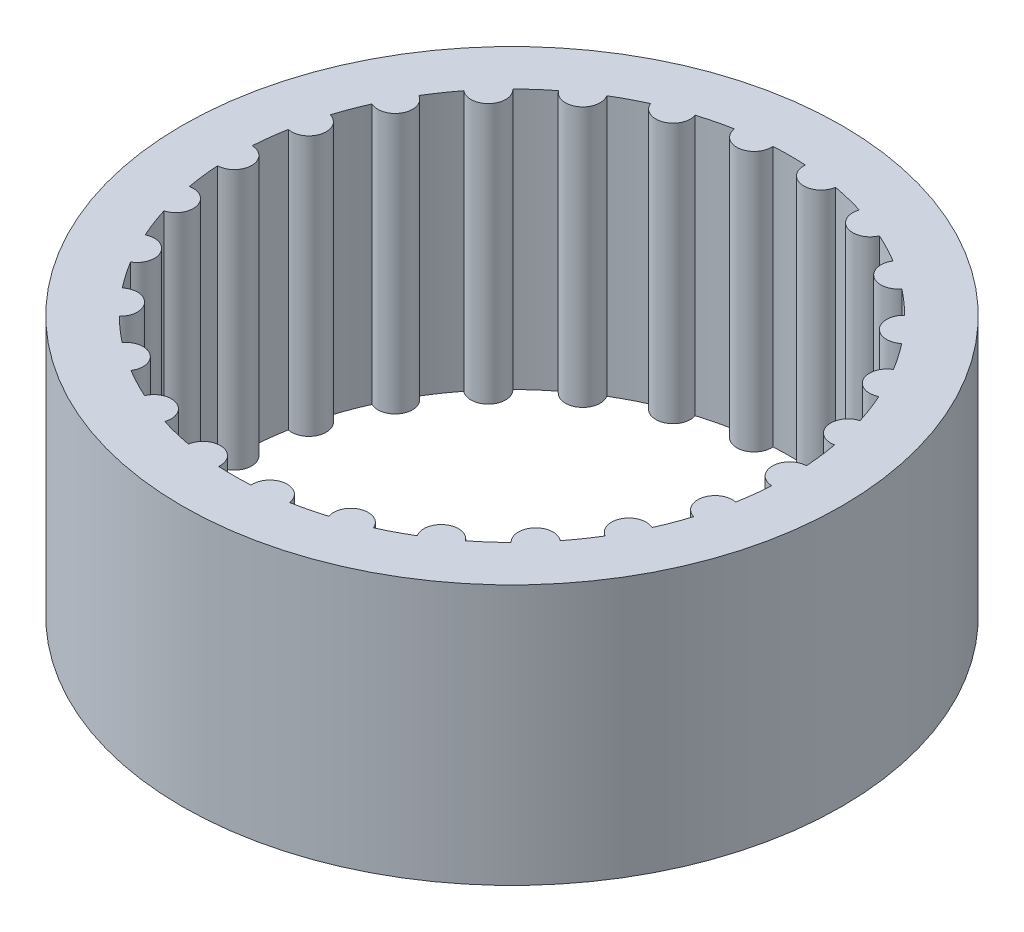
SolidWorks part; units mm, degrees
ref_plane "Front Plane" through (0, 0, 0) normal (0, 0, 1) x (1, 0, 0)
ref_plane "Top Plane" through (0, 0, 0) normal (0, 1, 0) x (1, 0, 0)
ref_plane "Right Plane" through (0, 0, 0) normal (1, 0, 0) x (0, 0, -1)
sketch "Sketch2" plane through (0, 0, 0) normal (0, 1, 0) x (1, 0, 0)
  line L0 (-15.4, 0) -> (14.4, 0) construction
  line L1 (0, 0) -> (0, -14.9128) construction
  line L2 (0, 0) -> (0, 14.9128) construction
  line L3 (-0.5, 0) -> (-0.5, -14.9128) construction
  line L4 (-0.5, 0) -> (-0.5, 14.9128) construction
  line L5 (14.4, 0) -> (15.5, 0) construction
  line L6 (0, 14.9128) -> (0, -14.9128) construction
  line L7 (5.9, 0) -> (9.1, 0) construction
  line L8 (5.9, 0) -> (7.5, 0)
  circle A0 centre (-0.5, 0) radius 16 construction
  circle A1 centre (15.5, 0) radius 1
  circle A2 centre (15.0351, -3.8291) radius 1
  circle A3 centre (13.6673, -7.4356) radius 1
  circle A4 centre (11.4762, -10.61) radius 1
  circle A5 centre (8.589, -13.1677) radius 1
  circle A6 centre (5.1737, -14.9603) radius 1
  circle A7 centre (1.4286, -15.8833) radius 1
  circle A8 centre (-2.4286, -15.8833) radius 1
  circle A9 centre (-6.1737, -14.9603) radius 1
  circle A10 centre (-9.589, -13.1677) radius 1
  circle A11 centre (-12.4762, -10.61) radius 1
  circle A12 centre (-14.6673, -7.4356) radius 1
  circle A13 centre (-16.0351, -3.8291) radius 1
  circle A14 centre (-16.5, 0) radius 1
  circle A15 centre (-16.0351, 3.8291) radius 1
  circle A16 centre (-14.6673, 7.4356) radius 1
  circle A17 centre (-12.4762, 10.61) radius 1
  circle A18 centre (-9.589, 13.1677) radius 1
  circle A19 centre (-6.1737, 14.9603) radius 1
  circle A20 centre (-2.4286, 15.8833) radius 1
  circle A21 centre (1.4286, 15.8833) radius 1
  circle A22 centre (5.1737, 14.9603) radius 1
  circle A23 centre (8.589, 13.1677) radius 1
  circle A24 centre (11.4762, 10.61) radius 1
  circle A25 centre (13.6673, 7.4356) radius 1
  circle A26 centre (15.0351, 3.8291) radius 1
  circle A27 centre (0, 0) radius 8
  circle A28 centre (8, 0) radius 2.1
  circle A29 centre (4, 6.9282) radius 2.1
  circle A30 centre (-4, 6.9282) radius 2.1
  circle A31 centre (-8, 0) radius 2.1
  circle A32 centre (-4, -6.9282) radius 2.1
  circle A33 centre (4, -6.9282) radius 2.1
  circle A34 centre (-1, 0) radius 8 construction
  circle A35 centre (3, -6.9282) radius 2.1
  circle A36 centre (-5, -6.9282) radius 2.1
  circle A37 centre (-9, 0) radius 2.1
  circle A38 centre (-5, 6.9282) radius 2.1
  circle A39 centre (3, 6.9282) radius 2.1
  circle A40 centre (7, 0) radius 2.1
  circle A41 centre (7.5, 0) radius 1.5
  circle A42 centre (3.5, -6.9282) radius 1.5
  circle A43 centre (-4.5, -6.9282) radius 1.5
  circle A44 centre (-8.5, 0) radius 1.5
  circle A45 centre (-4.5, 6.9282) radius 1.5
  circle A46 centre (3.5, 6.9282) radius 1.5
  spline S0 degree 4 poles (14.1521, 3.1658) (14.188, 3.1199) (14.2658, 3.0332) (14.3775, 2.9384) (14.515, 2.8555) (14.6203, 2.806) (14.6874, 2.778) (14.7412, 2.7556) (14.7939, 2.7309) (14.8442, 2.7016) (14.9616, 2.6171) (15.116, 2.4418) (15.2531, 2.163) (15.3044, 1.8261) (15.2781, 1.5454) (15.2134, 1.3341) (15.1457, 1.199) (15.0717, 1.0959) (14.999, 1.0246) (14.9346, 0.9749) (14.8529, 0.9144) (14.7598, 0.8351) (14.6613, 0.7318) (14.5658, 0.5985) (14.4899, 0.4547) (14.4445, 0.3242) (14.4198, 0.2202) (14.4058, 0.1237) (14.3997, 0.036) (14.399, -0.0233) (14.4055, -0.1232) (14.4175, -0.2057) (14.4353, -0.2848) (14.4589, -0.3638) (14.4955, -0.4601) (14.5538, -0.5777) (14.629, -0.6905) (14.7205, -0.7952) (14.8099, -0.8785) (14.886, -0.9397) (14.9653, -0.9969) (15.0394, -1.0608) (15.1018, -1.1365) (15.1543, -1.2193) (15.2086, -1.3292) (15.2563, -1.4688) (15.2881, -1.6381) (15.2945, -1.881) (15.2523, -2.1199) (15.1638, -2.3444) (15.0424, -2.5231) (14.9425, -2.6287) (14.8453, -2.7036) (14.7572, -2.7504) (14.6644, -2.7867) (14.5734, -2.827) (14.4636, -2.8857) (14.309, -2.9902) (14.1305, -3.1658) (13.9721, -3.435) (13.894, -3.7733) (13.9169, -4.0803) (13.9952, -4.3102) (14.0824, -4.4685) (14.1503, -4.5677) (14.21, -4.6429) (14.2706, -4.7176) (14.3202, -4.8002) (14.3654, -4.9109) (14.3993, -5.0496) (14.4169, -5.2624) (14.3843, -5.5009) (14.3041, -5.731) (14.178, -5.9418) (14.0479, -6.0957) (13.9108, -6.2086) (13.7771, -6.2844) (13.6546, -6.3259) (13.5506, -6.3413) (13.4467, -6.3556) (13.3441, -6.3782) (13.2186, -6.4164) (13.0491, -6.4902) (12.8504, -6.6239) (12.6494, -6.8484) (12.5061, -7.1523) (12.463, -7.451) (12.49, -7.6921) (12.5392, -7.8624) (12.5803, -7.968) (12.6183, -8.0504) (12.6544, -8.1336) (12.6783, -8.2214) (12.6929, -8.336) (12.6907, -8.4762) (12.6543, -8.6855) (12.5452, -8.9512) (12.3731, -9.1837) (12.1492, -9.3663) (11.9533, -9.4633) (11.8116, -9.5062) (11.6867, -9.5225) (11.5835, -9.517) (11.4812, -9.5034) (11.3782, -9.4969) (11.2749, -9.4982) (11.1721, -9.508) (11.0085, -9.5382) (10.791, -9.6158) (10.5438, -9.7787) (10.3474, -10.0243) (10.2402, -10.2686) (10.1943, -10.4842) (10.1853, -10.6384) (10.1931, -10.7705) (10.2091, -10.8795) (10.2256, -10.9662) (10.236, -11.0539) (10.2331, -11.1423) (10.2158, -11.2534) (10.1767, -11.3842) (10.0886, -11.5718) (9.9146, -11.8006) (9.6439, -12.0158) (9.3384, -12.1314) (9.0923, -12.1519) (8.9388, -12.1247) (8.8741, -12.1049) (8.8233, -12.0863) (8.76, -12.0622) (8.6577, -12.0268) (8.5127, -11.9913) (8.2954, -11.971) (8.0233, -12.0058) (7.7397, -12.12) (7.4775, -12.3303) (7.3093, -12.5758) (7.2277, -12.7964) (7.1948, -12.9647) (7.1831, -13.0729) (7.1774, -13.16) (7.1639, -13.2682) (7.1207, -13.3961) (7.0432, -13.5357) (6.8963, -13.7154) (6.6678, -13.8963) (6.3478, -14.0387) (6.02, -14.0727) (5.7619, -14.0269) (5.5985, -13.9438) (5.5126, -13.8801) (5.4018, -13.8057) (5.2599, -13.7303) (5.0524, -13.6565) (4.7738, -13.623) (4.4626, -13.6683) (4.1888, -13.7999) (3.9912, -13.9665) (3.8578, -14.1339) (3.7826, -14.2632) (3.7309, -14.3799) (3.6959, -14.48) (3.6689, -14.5606) (3.6251, -14.6573) (3.5494, -14.7647) (3.44, -14.8752) (3.2557, -15.006) (2.9928, -15.1201) (2.6515, -15.1757) (2.3406, -15.1291) (2.1258, -15.0338) (2.011, -14.9468) (1.9698, -14.909) (1.9317, -14.8681) (1.8954, -14.8255) (1.8499, -14.7726) (1.7735, -14.691) (1.6576, -14.5893) (1.4677, -14.4687) (1.2013, -14.3748) (0.8943, -14.3518) (0.5705, -14.4236) (0.3173, -14.5632) (0.1515, -14.7141) (0.0481, -14.8418) (-0.0114, -14.9289) (-0.057, -15.0001) (-0.1205, -15.0845) (-0.2167, -15.1711) (-0.3455, -15.2521) (-0.5484, -15.3356) (-0.8128, -15.3854) (-1.084, -15.3726) (-1.345, -15.2972) (-1.5435, -15.1922) (-1.6658, -15.0976) (-1.7547, -15.002) (-1.8112, -14.9128) (-1.8483, -14.8369) (-1.8948, -14.7422) (-1.9811, -14.5964) (-2.1305, -14.4153) (-2.3717, -14.2374) (-2.6941, -14.1243) (-3.0058, -14.1121) (-3.2798, -14.1742) (-3.4814, -14.2713) (-3.6077, -14.3581) (-3.6929, -14.4296) (-3.7443, -14.4763) (-3.7855, -14.5136) (-3.839, -14.5578) (-3.9718, -14.6426) (-4.2092, -14.7163) (-4.5379, -14.7232) (-4.871, -14.6233) (-5.1192, -14.4741) (-5.2872, -14.3161) (-5.3818, -14.1888) (-5.4416, -14.0686) (-5.4698, -13.9639) (-5.4862, -13.8788) (-5.5106, -13.7734) (-5.5628, -13.6112) (-5.6686, -13.4029) (-5.8615, -13.1808) (-6.1409, -13.0036) (-6.4324, -12.9205) (-6.707, -12.9139) (-6.9246, -12.958) (-7.0705, -13.0119) (-7.1719, -13.0612) (-7.2342, -13.0943) (-7.2842, -13.1203) (-7.3485, -13.1494) (-7.4504, -13.1813) (-7.5929, -13.1993) (-7.8225, -13.1875) (-8.1082, -13.1019) (-8.3607, -12.9481) (-8.5641, -12.7393) (-8.6869, -12.541) (-8.7459, -12.3913) (-8.7711, -12.2579) (-8.7697, -12.1482) (-8.7645, -12.0606) (-8.7633, -11.951) (-8.7731, -11.8212) (-8.8019, -11.6732) (-8.8729, -11.4717) (-9.0045, -11.25) (-9.2205, -11.0351) (-9.4997, -10.8905) (-9.7475, -10.8369) (-9.9383, -10.8322) (-10.0675, -10.8437) (-10.1698, -10.8609) (-10.2704, -10.8859) (-10.3717, -10.9089) (-10.4995, -10.9144) (-10.6499, -10.893) (-10.8644, -10.8236) (-11.1154, -10.6702) (-11.3185, -10.4608) (-11.4614, -10.2119) (-11.5248, -10.0134) (-11.5464, -9.8777) (-11.5487, -9.7646) (-11.5393, -9.6761) (-11.5169, -9.5902) (-11.4896, -9.5058) (-11.4606, -9.3988) (-11.4371, -9.2678) (-11.428, -9.1126) (-11.4489, -8.8917) (-11.5253, -8.6444) (-11.6806, -8.3917) (-11.9083, -8.1893) (-12.1461, -8.0664) (-12.3515, -8.0112) (-12.509, -7.9918) (-12.6408, -7.9895) (-12.7466, -7.9882) (-12.8744, -7.9638) (-13.0178, -7.9059) (-13.1692, -7.8114) (-13.319, -7.6747) (-13.472, -7.4805) (-13.5815, -7.2609) (-13.644, -7.0266) (-13.6529, -6.8129) (-13.6365, -6.6729) (-13.6064, -6.5605) (-13.5704, -6.4764) (-13.5232, -6.3982) (-13.4752, -6.3206) (-13.4215, -6.2199) (-13.3522, -6.0556) (-13.2972, -5.8178) (-13.3061, -5.5112) (-13.4183, -5.1858) (-13.5996, -4.9373) (-13.7884, -4.7826) (-13.9504, -4.6931) (-14.068, -4.6441) (-14.1647, -4.6121) (-14.2634, -4.587) (-14.3606, -4.5562) (-14.4721, -4.4972) (-14.5906, -4.4054) (-14.7415, -4.2409) (-14.8856, -3.984) (-14.9605, -3.7) (-14.9625, -3.4094) (-14.9171, -3.1994) (-14.8649, -3.0656) (-14.8048, -2.9613) (-14.7437, -2.886) (-14.6735, -2.8194) (-14.6048, -2.7515) (-14.5411, -2.6786) (-14.4829, -2.6013) (-14.3984, -2.4684) (-14.3099, -2.2678) (-14.2572, -1.9916) (-14.2948, -1.6527) (-14.4157, -1.3725) (-14.5648, -1.1806) (-14.7009, -1.0585) (-14.8015, -0.9857) (-14.886, -0.9336) (-14.9732, -0.8861) (-15.056, -0.8309) (-15.1453, -0.7457) (-15.2341, -0.6279) (-15.3021, -0.4979) (-15.3506, -0.3595) (-15.3784, -0.2422) (-15.3932, -0.1473) (-15.4005, -0.038) (-15.4007, 0.0312) (-15.3943, 0.133) (-15.3819, 0.2227) (-15.3632, 0.3082) (-15.3383, 0.3938) (-15.2991, 0.498) (-15.241, 0.614) (-15.1569, 0.7356) (-15.0521, 0.8388) (-14.947, 0.9) (-14.8417, 0.9596) (-14.7374, 1.0292) (-14.6222, 1.1253) (-14.4762, 1.2888) (-14.3483, 1.5104) (-14.2696, 1.788) (-14.2718, 2.0824) (-14.3338, 2.3297) (-14.4228, 2.5131) (-14.5089, 2.6398) (-14.5912, 2.7371) (-14.6628, 2.8095) (-14.7315, 2.8736) (-14.7874, 2.9388) (-14.8392, 3.0187) (-14.9, 3.1445) (-14.933, 3.2628) (-14.9484, 3.3663) (-14.9531, 3.4358) knots 0 0 0 0 0 0.003662 0.007324 0.009155 0.010071 0.010986 0.011902 0.012818 0.013733 0.014649 0.020984 0.02732 0.032959 0.035778 0.038598 0.041156 0.042436 0.043715 0.044995 0.046274 0.048833 0.051398 0.053964 0.05653 0.059096 0.059963 0.060831 0.062566 0.06386 0.065154 0.066448 0.067743 0.069037 0.070331 0.072919 0.075992 0.077529 0.079065 0.080602 0.082139 0.083675 0.085212 0.086754 0.088296 0.09138 0.094464 0.097548 0.103529 0.106519 0.10951 0.111075 0.112641 0.114207 0.115773 0.117339 0.118905 0.122036 0.127492 0.132948 0.138255 0.143562 0.146585 0.148096 0.149608 0.151119 0.15263 0.154142 0.155653 0.158618 0.161583 0.167513 0.170668 0.173824 0.176979 0.180135 0.181785 0.183435 0.185086 0.186736 0.188387 0.190037 0.193338 0.198334 0.203329 0.208757 0.214186 0.217039 0.218465 0.219892 0.221319 0.222745 0.224172 0.225598 0.228568 0.231538 0.237477 0.243509 0.246525 0.249541 0.251164 0.252787 0.25441 0.256033 0.257656 0.259279 0.260902 0.262525 0.268116 0.273708 0.279232 0.281995 0.284757 0.287531 0.288919 0.290306 0.291693 0.293081 0.294468 0.295855 0.298752 0.301648 0.307441 0.313806 0.320171 0.321875 0.322726 0.323578 0.32443 0.325282 0.326985 0.330392 0.333799 0.338942 0.344084 0.349371 0.354658 0.3574 0.358771 0.360142 0.361513 0.362884 0.365627 0.368572 0.371516 0.377406 0.383828 0.390249 0.39193 0.393611 0.395291 0.396972 0.400333 0.403695 0.409076 0.414457 0.419833 0.422521 0.425209 0.427878 0.429213 0.430548 0.431883 0.433218 0.435887 0.438758 0.441629 0.44737 0.453781 0.460191 0.46107 0.46195 0.462829 0.463708 0.464587 0.465466 0.467225 0.470742 0.474259 0.479542 0.484825 0.489836 0.494847 0.497504 0.498832 0.500161 0.501489 0.502818 0.505475 0.508247 0.51102 0.516564 0.52227 0.525123 0.527976 0.530631 0.531959 0.533286 0.534614 0.535941 0.538597 0.543936 0.549276 0.554531 0.559787 0.563284 0.566782 0.568531 0.569405 0.570279 0.571154 0.572028 0.573777 0.580153 0.586529 0.592383 0.595311 0.598238 0.600963 0.602326 0.603688 0.605051 0.606414 0.609139 0.614393 0.619646 0.62466 0.629675 0.633224 0.636772 0.638547 0.639434 0.640321 0.641208 0.642095 0.64387 0.647026 0.650182 0.656494 0.66242 0.665383 0.668345 0.671105 0.672484 0.673864 0.675243 0.676623 0.679382 0.682041 0.684701 0.690021 0.695473 0.700926 0.704188 0.705819 0.70745 0.709081 0.710712 0.712344 0.713975 0.717095 0.720216 0.726458 0.732287 0.735201 0.738116 0.739511 0.740907 0.742302 0.743698 0.745093 0.746488 0.749279 0.752059 0.754839 0.760398 0.765424 0.770449 0.773769 0.777088 0.778748 0.780408 0.782068 0.783727 0.786901 0.790075 0.793249 0.796422 0.802397 0.805385 0.808372 0.809808 0.811244 0.812679 0.814115 0.81555 0.816986 0.819857 0.825318 0.830779 0.83599 0.841201 0.844404 0.846006 0.847607 0.849209 0.850811 0.852412 0.854014 0.857107 0.8602 0.866387 0.872353 0.875336 0.878319 0.87984 0.881361 0.882882 0.884402 0.885923 0.887444 0.888965 0.890486 0.895823 0.90116 0.906397 0.911634 0.914757 0.916319 0.91788 0.919441 0.921003 0.922564 0.924126 0.927182 0.930238 0.931767 0.933295 0.934823 0.936351 0.937751 0.93915 0.940549 0.941949 0.943348 0.944747 0.947546 0.950087 0.952628 0.953898 0.955168 0.957709 0.960509 0.96331 0.96891 0.973663 0.978415 0.981621 0.984826 0.986428 0.988031 0.989634 0.991236 0.992332 0.993427 0.995618 1 1 1 1 1 construction
  spline S1 degree 4 poles (14.4, 0) (14.4, -0.018) (14.401, -0.0542) (14.4055, -0.1232) (14.4175, -0.2057) (14.4353, -0.2848) (14.4589, -0.3638) (14.4955, -0.4601) (14.5538, -0.5777) (14.629, -0.6905) (14.7205, -0.7952) (14.8099, -0.8785) (14.886, -0.9397) (14.9653, -0.9969) (15.0394, -1.0608) (15.1018, -1.1365) (15.1543, -1.2193) (15.2086, -1.3292) (15.2563, -1.4688) (15.2881, -1.6381) (15.2945, -1.881) (15.2523, -2.1199) (15.1638, -2.3444) (15.0424, -2.5231) (14.9425, -2.6287) (14.8453, -2.7036) (14.7572, -2.7504) (14.6644, -2.7867) (14.5734, -2.827) (14.4636, -2.8857) (14.309, -2.9902) (14.1305, -3.1658) (13.9721, -3.435) (13.894, -3.7733) (13.9169, -4.0803) (13.9952, -4.3102) (14.0824, -4.4685) (14.1503, -4.5677) (14.21, -4.6429) (14.2706, -4.7176) (14.3202, -4.8002) (14.3654, -4.9109) (14.3993, -5.0496) (14.4169, -5.2624) (14.3843, -5.5009) (14.3041, -5.731) (14.178, -5.9418) (14.0479, -6.0957) (13.9108, -6.2086) (13.7771, -6.2844) (13.6546, -6.3259) (13.5506, -6.3413) (13.4467, -6.3556) (13.3441, -6.3782) (13.2186, -6.4164) (13.0491, -6.4902) (12.8504, -6.6239) (12.6494, -6.8484) (12.5061, -7.1523) (12.463, -7.451) (12.49, -7.6921) (12.5392, -7.8624) (12.5803, -7.968) (12.6183, -8.0504) (12.6544, -8.1336) (12.6783, -8.2214) (12.6929, -8.336) (12.6907, -8.4762) (12.6543, -8.6855) (12.5452, -8.9512) (12.3731, -9.1837) (12.1492, -9.3663) (11.9533, -9.4633) (11.8116, -9.5062) (11.6867, -9.5225) (11.5835, -9.517) (11.4812, -9.5034) (11.3782, -9.4969) (11.2749, -9.4982) (11.1721, -9.508) (11.0085, -9.5382) (10.791, -9.6158) (10.5438, -9.7787) (10.3474, -10.0243) (10.2402, -10.2686) (10.1943, -10.4842) (10.1853, -10.6384) (10.1931, -10.7705) (10.2091, -10.8795) (10.2256, -10.9662) (10.236, -11.0539) (10.2331, -11.1423) (10.2158, -11.2534) (10.1767, -11.3842) (10.0886, -11.5718) (9.9146, -11.8006) (9.6439, -12.0158) (9.3384, -12.1314) (9.0923, -12.1519) (8.9388, -12.1247) (8.8741, -12.1049) (8.8233, -12.0863) (8.76, -12.0622) (8.6577, -12.0268) (8.5127, -11.9913) (8.2954, -11.971) (8.0233, -12.0058) (7.7397, -12.12) (7.4775, -12.3303) (7.3093, -12.5758) (7.2277, -12.7964) (7.1948, -12.9647) (7.1831, -13.0729) (7.1774, -13.16) (7.1639, -13.2682) (7.1207, -13.3961) (7.0432, -13.5357) (6.8963, -13.7154) (6.6678, -13.8963) (6.3478, -14.0387) (6.02, -14.0727) (5.7619, -14.0269) (5.5985, -13.9438) (5.5126, -13.8801) (5.4018, -13.8057) (5.2599, -13.7303) (5.0524, -13.6565) (4.7738, -13.623) (4.4626, -13.6683) (4.1888, -13.7999) (3.9912, -13.9665) (3.8578, -14.1339) (3.7826, -14.2632) (3.7309, -14.3799) (3.6959, -14.48) (3.6689, -14.5606) (3.6251, -14.6573) (3.5494, -14.7647) (3.44, -14.8752) (3.2557, -15.006) (2.9928, -15.1201) (2.6515, -15.1757) (2.3406, -15.1291) (2.1258, -15.0338) (2.011, -14.9468) (1.9698, -14.909) (1.9317, -14.8681) (1.8954, -14.8255) (1.8499, -14.7726) (1.7735, -14.691) (1.6576, -14.5893) (1.4677, -14.4687) (1.2013, -14.3748) (0.8943, -14.3518) (0.5705, -14.4236) (0.3173, -14.5632) (0.1515, -14.7141) (0.0481, -14.8418) (-0.0114, -14.9289) (-0.057, -15.0001) (-0.1205, -15.0845) (-0.2167, -15.1711) (-0.3455, -15.2521) (-0.5484, -15.3356) (-0.8128, -15.3854) (-1.084, -15.3726) (-1.345, -15.2972) (-1.5435, -15.1922) (-1.6658, -15.0976) (-1.7547, -15.002) (-1.8112, -14.9128) (-1.8483, -14.8369) (-1.8948, -14.7422) (-1.9811, -14.5964) (-2.1305, -14.4153) (-2.3717, -14.2374) (-2.6941, -14.1243) (-3.0058, -14.1121) (-3.2798, -14.1742) (-3.4814, -14.2713) (-3.6077, -14.3581) (-3.6929, -14.4296) (-3.7443, -14.4763) (-3.7855, -14.5136) (-3.839, -14.5578) (-3.9718, -14.6426) (-4.2092, -14.7163) (-4.5379, -14.7232) (-4.871, -14.6233) (-5.1192, -14.4741) (-5.2872, -14.3161) (-5.3818, -14.1888) (-5.4416, -14.0686) (-5.4698, -13.9639) (-5.4862, -13.8788) (-5.5106, -13.7734) (-5.5628, -13.6112) (-5.6686, -13.4029) (-5.8615, -13.1808) (-6.1409, -13.0036) (-6.4324, -12.9205) (-6.707, -12.9139) (-6.9246, -12.958) (-7.0705, -13.0119) (-7.1719, -13.0612) (-7.2342, -13.0943) (-7.2842, -13.1203) (-7.3485, -13.1494) (-7.4504, -13.1813) (-7.5929, -13.1993) (-7.8225, -13.1875) (-8.1082, -13.1019) (-8.3607, -12.9481) (-8.5641, -12.7393) (-8.6869, -12.541) (-8.7459, -12.3913) (-8.7711, -12.2579) (-8.7697, -12.1482) (-8.7645, -12.0606) (-8.7633, -11.951) (-8.7731, -11.8212) (-8.8019, -11.6732) (-8.8729, -11.4717) (-9.0045, -11.25) (-9.2205, -11.0351) (-9.4997, -10.8905) (-9.7475, -10.8369) (-9.9383, -10.8322) (-10.0675, -10.8437) (-10.1698, -10.8609) (-10.2704, -10.8859) (-10.3717, -10.9089) (-10.4995, -10.9144) (-10.6499, -10.893) (-10.8644, -10.8236) (-11.1154, -10.6702) (-11.3185, -10.4608) (-11.4614, -10.2119) (-11.5248, -10.0134) (-11.5464, -9.8777) (-11.5487, -9.7646) (-11.5393, -9.6761) (-11.5169, -9.5902) (-11.4896, -9.5058) (-11.4606, -9.3988) (-11.4371, -9.2678) (-11.428, -9.1126) (-11.4489, -8.8917) (-11.5253, -8.6444) (-11.6806, -8.3917) (-11.9083, -8.1893) (-12.1461, -8.0664) (-12.3515, -8.0112) (-12.509, -7.9918) (-12.6408, -7.9895) (-12.7466, -7.9882) (-12.8744, -7.9638) (-13.0178, -7.9059) (-13.1692, -7.8114) (-13.319, -7.6747) (-13.472, -7.4805) (-13.5815, -7.2609) (-13.644, -7.0266) (-13.6529, -6.8129) (-13.6365, -6.6729) (-13.6064, -6.5605) (-13.5704, -6.4764) (-13.5232, -6.3982) (-13.4752, -6.3206) (-13.4215, -6.2199) (-13.3522, -6.0556) (-13.2972, -5.8178) (-13.3061, -5.5112) (-13.4183, -5.1858) (-13.5996, -4.9373) (-13.7884, -4.7826) (-13.9504, -4.6931) (-14.068, -4.6441) (-14.1647, -4.6121) (-14.2634, -4.587) (-14.3606, -4.5562) (-14.4721, -4.4972) (-14.5906, -4.4054) (-14.7415, -4.2409) (-14.8856, -3.984) (-14.9605, -3.7) (-14.9625, -3.4094) (-14.9171, -3.1994) (-14.8649, -3.0656) (-14.8048, -2.9613) (-14.7437, -2.886) (-14.6735, -2.8194) (-14.6048, -2.7515) (-14.5411, -2.6786) (-14.4829, -2.6013) (-14.3984, -2.4684) (-14.3099, -2.2678) (-14.2572, -1.9916) (-14.2948, -1.6527) (-14.4157, -1.3725) (-14.5648, -1.1806) (-14.7009, -1.0585) (-14.8015, -0.9857) (-14.886, -0.9336) (-14.9732, -0.8861) (-15.056, -0.8309) (-15.1453, -0.7457) (-15.2341, -0.6279) (-15.3021, -0.4979) (-15.3506, -0.3595) (-15.3784, -0.2422) (-15.3932, -0.1473) (-15.3988, -0.0635) (-15.4, -0.0212) (-15.4, 0) knots 0.062566 0.062566 0.062566 0.062566 0.062566 0.06386 0.065154 0.066448 0.067743 0.069037 0.070331 0.072919 0.075992 0.077529 0.079065 0.080602 0.082139 0.083675 0.085212 0.086754 0.088296 0.09138 0.094464 0.097548 0.103529 0.106519 0.10951 0.111075 0.112641 0.114207 0.115773 0.117339 0.118905 0.122036 0.127492 0.132948 0.138255 0.143562 0.146585 0.148096 0.149608 0.151119 0.15263 0.154142 0.155653 0.158618 0.161583 0.167513 0.170668 0.173824 0.176979 0.180135 0.181785 0.183435 0.185086 0.186736 0.188387 0.190037 0.193338 0.198334 0.203329 0.208757 0.214186 0.217039 0.218465 0.219892 0.221319 0.222745 0.224172 0.225598 0.228568 0.231538 0.237477 0.243509 0.246525 0.249541 0.251164 0.252787 0.25441 0.256033 0.257656 0.259279 0.260902 0.262525 0.268116 0.273708 0.279232 0.281995 0.284757 0.287531 0.288919 0.290306 0.291693 0.293081 0.294468 0.295855 0.298752 0.301648 0.307441 0.313806 0.320171 0.321875 0.322726 0.323578 0.32443 0.325282 0.326985 0.330392 0.333799 0.338942 0.344084 0.349371 0.354658 0.3574 0.358771 0.360142 0.361513 0.362884 0.365627 0.368572 0.371516 0.377406 0.383828 0.390249 0.39193 0.393611 0.395291 0.396972 0.400333 0.403695 0.409076 0.414457 0.419833 0.422521 0.425209 0.427878 0.429213 0.430548 0.431883 0.433218 0.435887 0.438758 0.441629 0.44737 0.453781 0.460191 0.46107 0.46195 0.462829 0.463708 0.464587 0.465466 0.467225 0.470742 0.474259 0.479542 0.484825 0.489836 0.494847 0.497504 0.498832 0.500161 0.501489 0.502818 0.505475 0.508247 0.51102 0.516564 0.52227 0.525123 0.527976 0.530631 0.531959 0.533286 0.534614 0.535941 0.538597 0.543936 0.549276 0.554531 0.559787 0.563284 0.566782 0.568531 0.569405 0.570279 0.571154 0.572028 0.573777 0.580153 0.586529 0.592383 0.595311 0.598238 0.600963 0.602326 0.603688 0.605051 0.606414 0.609139 0.614393 0.619646 0.62466 0.629675 0.633224 0.636772 0.638547 0.639434 0.640321 0.641208 0.642095 0.64387 0.647026 0.650182 0.656494 0.66242 0.665383 0.668345 0.671105 0.672484 0.673864 0.675243 0.676623 0.679382 0.682041 0.684701 0.690021 0.695473 0.700926 0.704188 0.705819 0.70745 0.709081 0.710712 0.712344 0.713975 0.717095 0.720216 0.726458 0.732287 0.735201 0.738116 0.739511 0.740907 0.742302 0.743698 0.745093 0.746488 0.749279 0.752059 0.754839 0.760398 0.765424 0.770449 0.773769 0.777088 0.778748 0.780408 0.782068 0.783727 0.786901 0.790075 0.793249 0.796422 0.802397 0.805385 0.808372 0.809808 0.811244 0.812679 0.814115 0.81555 0.816986 0.819857 0.825318 0.830779 0.83599 0.841201 0.844404 0.846006 0.847607 0.849209 0.850811 0.852412 0.854014 0.857107 0.8602 0.866387 0.872353 0.875336 0.878319 0.87984 0.881361 0.882882 0.884402 0.885923 0.887444 0.888965 0.890486 0.895823 0.90116 0.906397 0.911634 0.914757 0.916319 0.91788 0.919441 0.921003 0.922564 0.924126 0.927182 0.930238 0.931767 0.933295 0.934823 0.936351 0.936351 0.936351 0.936351 0.936351
  spline S2 degree 4 poles (14.4, 0) (14.4, 0.018) (14.401, 0.0542) (14.4055, 0.1232) (14.4175, 0.2057) (14.4353, 0.2848) (14.4589, 0.3638) (14.4955, 0.4601) (14.5538, 0.5777) (14.629, 0.6905) (14.7205, 0.7952) (14.8099, 0.8785) (14.886, 0.9397) (14.9653, 0.9969) (15.0394, 1.0608) (15.1018, 1.1365) (15.1543, 1.2193) (15.2086, 1.3292) (15.2563, 1.4688) (15.2881, 1.6381) (15.2945, 1.881) (15.2523, 2.1199) (15.1638, 2.3444) (15.0424, 2.5231) (14.9425, 2.6287) (14.8453, 2.7036) (14.7572, 2.7504) (14.6644, 2.7867) (14.5734, 2.827) (14.4636, 2.8857) (14.309, 2.9902) (14.1305, 3.1658) (13.9721, 3.435) (13.894, 3.7733) (13.9169, 4.0803) (13.9952, 4.3102) (14.0824, 4.4685) (14.1503, 4.5677) (14.21, 4.6429) (14.2706, 4.7176) (14.3202, 4.8002) (14.3654, 4.9109) (14.3993, 5.0496) (14.4169, 5.2624) (14.3843, 5.5009) (14.3041, 5.731) (14.178, 5.9418) (14.0479, 6.0957) (13.9108, 6.2086) (13.7771, 6.2844) (13.6546, 6.3259) (13.5506, 6.3413) (13.4467, 6.3556) (13.3441, 6.3782) (13.2186, 6.4164) (13.0491, 6.4902) (12.8504, 6.6239) (12.6494, 6.8484) (12.5061, 7.1523) (12.463, 7.451) (12.49, 7.6921) (12.5392, 7.8624) (12.5803, 7.968) (12.6183, 8.0504) (12.6544, 8.1336) (12.6783, 8.2214) (12.6929, 8.336) (12.6907, 8.4762) (12.6543, 8.6855) (12.5452, 8.9512) (12.3731, 9.1837) (12.1492, 9.3663) (11.9533, 9.4633) (11.8116, 9.5062) (11.6867, 9.5225) (11.5835, 9.517) (11.4812, 9.5034) (11.3782, 9.4969) (11.2749, 9.4982) (11.1721, 9.508) (11.0085, 9.5382) (10.791, 9.6158) (10.5438, 9.7787) (10.3474, 10.0243) (10.2402, 10.2686) (10.1943, 10.4842) (10.1853, 10.6384) (10.1931, 10.7705) (10.2091, 10.8795) (10.2256, 10.9662) (10.236, 11.0539) (10.2331, 11.1423) (10.2158, 11.2534) (10.1767, 11.3842) (10.0886, 11.5718) (9.9146, 11.8006) (9.6439, 12.0158) (9.3384, 12.1314) (9.0923, 12.1519) (8.9388, 12.1247) (8.8741, 12.1049) (8.8233, 12.0863) (8.76, 12.0622) (8.6577, 12.0268) (8.5127, 11.9913) (8.2954, 11.971) (8.0233, 12.0058) (7.7397, 12.12) (7.4775, 12.3303) (7.3093, 12.5758) (7.2277, 12.7964) (7.1948, 12.9647) (7.1831, 13.0729) (7.1774, 13.16) (7.1639, 13.2682) (7.1207, 13.3961) (7.0432, 13.5357) (6.8963, 13.7154) (6.6678, 13.8963) (6.3478, 14.0387) (6.02, 14.0727) (5.7619, 14.0269) (5.5985, 13.9438) (5.5126, 13.8801) (5.4018, 13.8057) (5.2599, 13.7303) (5.0524, 13.6565) (4.7738, 13.623) (4.4626, 13.6683) (4.1888, 13.7999) (3.9912, 13.9665) (3.8578, 14.1339) (3.7826, 14.2632) (3.7309, 14.3799) (3.6959, 14.48) (3.6689, 14.5606) (3.6251, 14.6573) (3.5494, 14.7647) (3.44, 14.8752) (3.2557, 15.006) (2.9928, 15.1201) (2.6515, 15.1757) (2.3406, 15.1291) (2.1258, 15.0338) (2.011, 14.9468) (1.9698, 14.909) (1.9317, 14.8681) (1.8954, 14.8255) (1.8499, 14.7726) (1.7735, 14.691) (1.6576, 14.5893) (1.4677, 14.4687) (1.2013, 14.3748) (0.8943, 14.3518) (0.5705, 14.4236) (0.3173, 14.5632) (0.1515, 14.7141) (0.0481, 14.8418) (-0.0114, 14.9289) (-0.057, 15) (-0.1205, 15.0845) (-0.2167, 15.1711) (-0.3455, 15.2521) (-0.5484, 15.3356) (-0.8128, 15.3854) (-1.084, 15.3726) (-1.345, 15.2972) (-1.5435, 15.1922) (-1.6658, 15.0976) (-1.7547, 15.002) (-1.8112, 14.9128) (-1.8483, 14.8369) (-1.8948, 14.7422) (-1.9811, 14.5964) (-2.1305, 14.4153) (-2.3717, 14.2374) (-2.6941, 14.1243) (-3.0058, 14.1121) (-3.2798, 14.1742) (-3.4814, 14.2713) (-3.6077, 14.3581) (-3.6929, 14.4296) (-3.7443, 14.4763) (-3.7855, 14.5136) (-3.839, 14.5578) (-3.9718, 14.6426) (-4.2092, 14.7163) (-4.5379, 14.7232) (-4.871, 14.6233) (-5.1192, 14.4741) (-5.2872, 14.3161) (-5.3818, 14.1887) (-5.4416, 14.0686) (-5.4698, 13.9639) (-5.4862, 13.8788) (-5.5106, 13.7734) (-5.5628, 13.6112) (-5.6686, 13.4029) (-5.8615, 13.1808) (-6.1409, 13.0036) (-6.4324, 12.9205) (-6.707, 12.9139) (-6.9246, 12.958) (-7.0705, 13.0119) (-7.1719, 13.0612) (-7.2342, 13.0943) (-7.2842, 13.1203) (-7.3485, 13.1494) (-7.4504, 13.1813) (-7.5929, 13.1993) (-7.8225, 13.1875) (-8.1082, 13.1019) (-8.3607, 12.9481) (-8.5641, 12.7393) (-8.6869, 12.541) (-8.7459, 12.3913) (-8.7711, 12.2579) (-8.7697, 12.1482) (-8.7645, 12.0606) (-8.7633, 11.951) (-8.7731, 11.8212) (-8.8019, 11.6732) (-8.8729, 11.4717) (-9.0045, 11.25) (-9.2205, 11.0351) (-9.4997, 10.8905) (-9.7475, 10.8369) (-9.9383, 10.8322) (-10.0675, 10.8437) (-10.1698, 10.8609) (-10.2704, 10.8859) (-10.3717, 10.9089) (-10.4995, 10.9144) (-10.6499, 10.893) (-10.8644, 10.8236) (-11.1154, 10.6702) (-11.3185, 10.4608) (-11.4614, 10.2119) (-11.5248, 10.0134) (-11.5464, 9.8777) (-11.5487, 9.7646) (-11.5393, 9.6761) (-11.5169, 9.5902) (-11.4896, 9.5058) (-11.4606, 9.3988) (-11.4371, 9.2678) (-11.428, 9.1126) (-11.4489, 8.8917) (-11.5253, 8.6444) (-11.6806, 8.3917) (-11.9083, 8.1893) (-12.1461, 8.0664) (-12.3515, 8.0112) (-12.509, 7.9918) (-12.6408, 7.9895) (-12.7466, 7.9882) (-12.8744, 7.9638) (-13.0178, 7.9059) (-13.1692, 7.8114) (-13.319, 7.6747) (-13.472, 7.4805) (-13.5815, 7.2609) (-13.644, 7.0266) (-13.6529, 6.8129) (-13.6365, 6.6728) (-13.6064, 6.5605) (-13.5704, 6.4764) (-13.5232, 6.3982) (-13.4752, 6.3206) (-13.4215, 6.2199) (-13.3522, 6.0556) (-13.2972, 5.8178) (-13.3061, 5.5112) (-13.4183, 5.1858) (-13.5996, 4.9373) (-13.7884, 4.7826) (-13.9504, 4.6931) (-14.068, 4.6441) (-14.1647, 4.6121) (-14.2634, 4.587) (-14.3606, 4.5562) (-14.4721, 4.4972) (-14.5906, 4.4054) (-14.7415, 4.2409) (-14.8856, 3.984) (-14.9605, 3.7) (-14.9625, 3.4094) (-14.9171, 3.1994) (-14.8649, 3.0655) (-14.8048, 2.9613) (-14.7437, 2.886) (-14.6735, 2.8194) (-14.6048, 2.7515) (-14.5411, 2.6786) (-14.4829, 2.6013) (-14.3984, 2.4684) (-14.3099, 2.2678) (-14.2572, 1.9916) (-14.2948, 1.6527) (-14.4157, 1.3725) (-14.5648, 1.1806) (-14.7009, 1.0585) (-14.8015, 0.9857) (-14.886, 0.9336) (-14.9732, 0.8861) (-15.056, 0.8309) (-15.1453, 0.7457) (-15.2341, 0.6279) (-15.3021, 0.4979) (-15.3506, 0.3595) (-15.3784, 0.2422) (-15.3932, 0.1473) (-15.3988, 0.0635) (-15.4, 0.0212) (-15.4, 0) knots 0.062566 0.062566 0.062566 0.062566 0.062566 0.06386 0.065154 0.066448 0.067743 0.069037 0.070331 0.072919 0.075992 0.077529 0.079065 0.080602 0.082139 0.083675 0.085212 0.086754 0.088296 0.09138 0.094464 0.097548 0.103529 0.106519 0.10951 0.111075 0.112641 0.114207 0.115773 0.117339 0.118905 0.122036 0.127492 0.132948 0.138255 0.143562 0.146585 0.148096 0.149608 0.151119 0.15263 0.154142 0.155653 0.158618 0.161583 0.167513 0.170668 0.173824 0.176979 0.180135 0.181785 0.183435 0.185086 0.186736 0.188387 0.190037 0.193338 0.198334 0.203329 0.208757 0.214186 0.217039 0.218465 0.219892 0.221319 0.222745 0.224172 0.225598 0.228568 0.231538 0.237477 0.243509 0.246525 0.249541 0.251164 0.252787 0.25441 0.256033 0.257656 0.259279 0.260902 0.262525 0.268116 0.273708 0.279232 0.281995 0.284757 0.287531 0.288919 0.290306 0.291693 0.293081 0.294468 0.295855 0.298752 0.301648 0.307441 0.313806 0.320171 0.321875 0.322726 0.323578 0.32443 0.325282 0.326985 0.330392 0.333799 0.338942 0.344084 0.349371 0.354658 0.3574 0.358771 0.360142 0.361513 0.362884 0.365627 0.368572 0.371516 0.377406 0.383828 0.390249 0.39193 0.393611 0.395291 0.396972 0.400333 0.403695 0.409076 0.414457 0.419833 0.422521 0.425209 0.427878 0.429213 0.430548 0.431883 0.433218 0.435887 0.438758 0.441629 0.44737 0.453781 0.460191 0.46107 0.46195 0.462829 0.463708 0.464587 0.465466 0.467225 0.470742 0.474259 0.479542 0.484825 0.489836 0.494847 0.497504 0.498832 0.500161 0.501489 0.502818 0.505475 0.508247 0.51102 0.516564 0.52227 0.525123 0.527976 0.530631 0.531959 0.533286 0.534614 0.535941 0.538597 0.543936 0.549276 0.554531 0.559787 0.563284 0.566782 0.568531 0.569405 0.570279 0.571154 0.572028 0.573777 0.580153 0.586529 0.592383 0.595311 0.598238 0.600963 0.602326 0.603688 0.605051 0.606414 0.609139 0.614393 0.619646 0.62466 0.629675 0.633224 0.636772 0.638547 0.639434 0.640321 0.641208 0.642095 0.64387 0.647026 0.650182 0.656494 0.66242 0.665383 0.668345 0.671105 0.672484 0.673864 0.675243 0.676623 0.679382 0.682041 0.684701 0.690021 0.695473 0.700926 0.704188 0.705819 0.70745 0.709081 0.710712 0.712344 0.713975 0.717095 0.720216 0.726458 0.732287 0.735201 0.738116 0.739511 0.740907 0.742302 0.743698 0.745093 0.746488 0.749279 0.752059 0.754839 0.760398 0.765424 0.770449 0.773769 0.777088 0.778748 0.780408 0.782068 0.783727 0.786901 0.790075 0.793249 0.796422 0.802397 0.805385 0.808372 0.809808 0.811244 0.812679 0.814115 0.81555 0.816986 0.819857 0.825318 0.830779 0.83599 0.841201 0.844404 0.846006 0.847607 0.849209 0.850811 0.852412 0.854014 0.857107 0.8602 0.866387 0.872353 0.875336 0.878319 0.87984 0.881361 0.882882 0.884402 0.885923 0.887444 0.888965 0.890486 0.895823 0.90116 0.906397 0.911634 0.914757 0.916319 0.91788 0.919441 0.921003 0.922564 0.924126 0.927182 0.930238 0.931767 0.933295 0.934823 0.936351 0.936351 0.936351 0.936351 0.936351
  spline S3 degree 4 poles (-15.4, 0) (-15.4, -0.018) (-15.401, -0.0542) (-15.4055, -0.1232) (-15.4175, -0.2057) (-15.4353, -0.2848) (-15.4589, -0.3638) (-15.4955, -0.4601) (-15.5538, -0.5777) (-15.629, -0.6905) (-15.7205, -0.7952) (-15.8099, -0.8785) (-15.886, -0.9397) (-15.9653, -0.9969) (-16.0394, -1.0608) (-16.1018, -1.1365) (-16.1543, -1.2193) (-16.2086, -1.3292) (-16.2563, -1.4688) (-16.2881, -1.6381) (-16.2945, -1.881) (-16.2523, -2.1199) (-16.1638, -2.3444) (-16.0424, -2.5231) (-15.9425, -2.6287) (-15.8453, -2.7036) (-15.7572, -2.7504) (-15.6644, -2.7867) (-15.5734, -2.827) (-15.4636, -2.8857) (-15.309, -2.9902) (-15.1305, -3.1658) (-14.9721, -3.435) (-14.894, -3.7733) (-14.9169, -4.0803) (-14.9952, -4.3102) (-15.0824, -4.4685) (-15.1503, -4.5677) (-15.21, -4.6429) (-15.2706, -4.7176) (-15.3202, -4.8002) (-15.3654, -4.9109) (-15.3993, -5.0496) (-15.4169, -5.2624) (-15.3843, -5.5009) (-15.3041, -5.731) (-15.178, -5.9418) (-15.0479, -6.0957) (-14.9108, -6.2086) (-14.7771, -6.2844) (-14.6546, -6.3259) (-14.5506, -6.3413) (-14.4467, -6.3556) (-14.3441, -6.3782) (-14.2186, -6.4164) (-14.0491, -6.4902) (-13.8504, -6.6239) (-13.6494, -6.8484) (-13.5061, -7.1523) (-13.463, -7.451) (-13.49, -7.6921) (-13.5392, -7.8624) (-13.5803, -7.968) (-13.6183, -8.0504) (-13.6544, -8.1336) (-13.6783, -8.2214) (-13.6929, -8.336) (-13.6907, -8.4762) (-13.6543, -8.6855) (-13.5452, -8.9512) (-13.3731, -9.1837) (-13.1492, -9.3663) (-12.9533, -9.4633) (-12.8116, -9.5062) (-12.6867, -9.5225) (-12.5835, -9.517) (-12.4812, -9.5034) (-12.3782, -9.4969) (-12.2749, -9.4982) (-12.1721, -9.508) (-12.0085, -9.5382) (-11.791, -9.6158) (-11.5438, -9.7787) (-11.3474, -10.0243) (-11.2402, -10.2686) (-11.1943, -10.4842) (-11.1853, -10.6384) (-11.1931, -10.7705) (-11.2091, -10.8795) (-11.2256, -10.9662) (-11.236, -11.0539) (-11.2331, -11.1423) (-11.2158, -11.2534) (-11.1767, -11.3842) (-11.0886, -11.5718) (-10.9146, -11.8006) (-10.6439, -12.0158) (-10.3384, -12.1314) (-10.0923, -12.1519) (-9.9388, -12.1247) (-9.8741, -12.1049) (-9.8233, -12.0863) (-9.76, -12.0622) (-9.6577, -12.0268) (-9.5127, -11.9913) (-9.2954, -11.971) (-9.0233, -12.0058) (-8.7397, -12.12) (-8.4775, -12.3303) (-8.3093, -12.5758) (-8.2277, -12.7964) (-8.1948, -12.9647) (-8.1831, -13.0729) (-8.1774, -13.16) (-8.1639, -13.2682) (-8.1207, -13.3961) (-8.0432, -13.5357) (-7.8963, -13.7154) (-7.6678, -13.8963) (-7.3478, -14.0387) (-7.02, -14.0727) (-6.7619, -14.0269) (-6.5985, -13.9438) (-6.5126, -13.8801) (-6.4018, -13.8057) (-6.2599, -13.7303) (-6.0524, -13.6565) (-5.7738, -13.623) (-5.4626, -13.6683) (-5.1888, -13.7999) (-4.9912, -13.9665) (-4.8578, -14.1339) (-4.7826, -14.2632) (-4.7309, -14.3799) (-4.6959, -14.48) (-4.6689, -14.5606) (-4.6251, -14.6573) (-4.5494, -14.7647) (-4.44, -14.8752) (-4.2557, -15.006) (-3.9928, -15.1201) (-3.6515, -15.1757) (-3.3406, -15.1291) (-3.1258, -15.0338) (-3.011, -14.9468) (-2.9698, -14.909) (-2.9317, -14.8681) (-2.8954, -14.8255) (-2.8499, -14.7726) (-2.7735, -14.691) (-2.6576, -14.5893) (-2.4677, -14.4687) (-2.2013, -14.3748) (-1.8943, -14.3518) (-1.5705, -14.4236) (-1.3173, -14.5632) (-1.1515, -14.7141) (-1.0481, -14.8418) (-0.9886, -14.9289) (-0.943, -15) (-0.8795, -15.0845) (-0.7833, -15.1711) (-0.6545, -15.2521) (-0.4516, -15.3356) (-0.1872, -15.3854) (0.084, -15.3726) (0.345, -15.2972) (0.5435, -15.1922) (0.6658, -15.0976) (0.7547, -15.002) (0.8112, -14.9128) (0.8483, -14.8369) (0.8948, -14.7422) (0.9811, -14.5964) (1.1305, -14.4153) (1.3717, -14.2374) (1.6941, -14.1243) (2.0058, -14.1121) (2.2798, -14.1742) (2.4814, -14.2713) (2.6077, -14.3581) (2.6929, -14.4296) (2.7443, -14.4763) (2.7855, -14.5136) (2.839, -14.5578) (2.9718, -14.6426) (3.2092, -14.7163) (3.5379, -14.7232) (3.871, -14.6233) (4.1192, -14.4741) (4.2872, -14.3161) (4.3818, -14.1887) (4.4416, -14.0686) (4.4698, -13.9639) (4.4862, -13.8788) (4.5106, -13.7734) (4.5628, -13.6112) (4.6686, -13.4029) (4.8615, -13.1808) (5.1409, -13.0036) (5.4324, -12.9205) (5.707, -12.9139) (5.9246, -12.958) (6.0705, -13.0119) (6.1719, -13.0612) (6.2342, -13.0943) (6.2842, -13.1203) (6.3485, -13.1494) (6.4504, -13.1813) (6.5929, -13.1993) (6.8225, -13.1875) (7.1082, -13.1019) (7.3607, -12.9481) (7.5641, -12.7393) (7.6869, -12.541) (7.7459, -12.3913) (7.7711, -12.2579) (7.7697, -12.1482) (7.7645, -12.0606) (7.7633, -11.951) (7.7731, -11.8212) (7.8019, -11.6732) (7.8729, -11.4717) (8.0045, -11.25) (8.2205, -11.0351) (8.4997, -10.8905) (8.7475, -10.8369) (8.9383, -10.8322) (9.0675, -10.8437) (9.1698, -10.8609) (9.2704, -10.8859) (9.3717, -10.9089) (9.4995, -10.9144) (9.6499, -10.893) (9.8644, -10.8236) (10.1154, -10.6702) (10.3185, -10.4608) (10.4614, -10.2119) (10.5248, -10.0134) (10.5464, -9.8777) (10.5487, -9.7646) (10.5393, -9.6761) (10.5169, -9.5902) (10.4896, -9.5058) (10.4606, -9.3988) (10.4371, -9.2678) (10.428, -9.1126) (10.4489, -8.8917) (10.5253, -8.6444) (10.6806, -8.3917) (10.9083, -8.1893) (11.1461, -8.0664) (11.3515, -8.0112) (11.509, -7.9918) (11.6408, -7.9895) (11.7466, -7.9882) (11.8744, -7.9638) (12.0178, -7.9059) (12.1692, -7.8114) (12.319, -7.6747) (12.472, -7.4805) (12.5815, -7.2609) (12.644, -7.0266) (12.6529, -6.8129) (12.6365, -6.6728) (12.6064, -6.5605) (12.5704, -6.4764) (12.5232, -6.3982) (12.4752, -6.3206) (12.4215, -6.2199) (12.3522, -6.0556) (12.2972, -5.8178) (12.3061, -5.5112) (12.4183, -5.1858) (12.5996, -4.9373) (12.7884, -4.7826) (12.9504, -4.6931) (13.068, -4.6441) (13.1647, -4.6121) (13.2634, -4.587) (13.3606, -4.5562) (13.4721, -4.4972) (13.5906, -4.4054) (13.7415, -4.2409) (13.8856, -3.984) (13.9605, -3.7) (13.9625, -3.4094) (13.9171, -3.1994) (13.8649, -3.0655) (13.8048, -2.9613) (13.7437, -2.886) (13.6735, -2.8194) (13.6048, -2.7515) (13.5411, -2.6786) (13.4829, -2.6013) (13.3984, -2.4684) (13.3099, -2.2678) (13.2572, -1.9916) (13.2948, -1.6527) (13.4157, -1.3725) (13.5648, -1.1806) (13.7009, -1.0585) (13.8015, -0.9857) (13.886, -0.9336) (13.9732, -0.8861) (14.056, -0.8309) (14.1453, -0.7457) (14.2341, -0.6279) (14.3021, -0.4979) (14.3506, -0.3595) (14.3784, -0.2422) (14.3932, -0.1473) (14.3988, -0.0635) (14.4, -0.0212) (14.4, 0) knots 0.062566 0.062566 0.062566 0.062566 0.062566 0.06386 0.065154 0.066448 0.067743 0.069037 0.070331 0.072919 0.075992 0.077529 0.079065 0.080602 0.082139 0.083675 0.085212 0.086754 0.088296 0.09138 0.094464 0.097548 0.103529 0.106519 0.10951 0.111075 0.112641 0.114207 0.115773 0.117339 0.118905 0.122036 0.127492 0.132948 0.138255 0.143562 0.146585 0.148096 0.149608 0.151119 0.15263 0.154142 0.155653 0.158618 0.161583 0.167513 0.170668 0.173824 0.176979 0.180135 0.181785 0.183435 0.185086 0.186736 0.188387 0.190037 0.193338 0.198334 0.203329 0.208757 0.214186 0.217039 0.218465 0.219892 0.221319 0.222745 0.224172 0.225598 0.228568 0.231538 0.237477 0.243509 0.246525 0.249541 0.251164 0.252787 0.25441 0.256033 0.257656 0.259279 0.260902 0.262525 0.268116 0.273708 0.279232 0.281995 0.284757 0.287531 0.288919 0.290306 0.291693 0.293081 0.294468 0.295855 0.298752 0.301648 0.307441 0.313806 0.320171 0.321875 0.322726 0.323578 0.32443 0.325282 0.326985 0.330392 0.333799 0.338942 0.344084 0.349371 0.354658 0.3574 0.358771 0.360142 0.361513 0.362884 0.365627 0.368572 0.371516 0.377406 0.383828 0.390249 0.39193 0.393611 0.395291 0.396972 0.400333 0.403695 0.409076 0.414457 0.419833 0.422521 0.425209 0.427878 0.429213 0.430548 0.431883 0.433218 0.435887 0.438758 0.441629 0.44737 0.453781 0.460191 0.46107 0.46195 0.462829 0.463708 0.464587 0.465466 0.467225 0.470742 0.474259 0.479542 0.484825 0.489836 0.494847 0.497504 0.498832 0.500161 0.501489 0.502818 0.505475 0.508247 0.51102 0.516564 0.52227 0.525123 0.527976 0.530631 0.531959 0.533286 0.534614 0.535941 0.538597 0.543936 0.549276 0.554531 0.559787 0.563284 0.566782 0.568531 0.569405 0.570279 0.571154 0.572028 0.573777 0.580153 0.586529 0.592383 0.595311 0.598238 0.600963 0.602326 0.603688 0.605051 0.606414 0.609139 0.614393 0.619646 0.62466 0.629675 0.633224 0.636772 0.638547 0.639434 0.640321 0.641208 0.642095 0.64387 0.647026 0.650182 0.656494 0.66242 0.665383 0.668345 0.671105 0.672484 0.673864 0.675243 0.676623 0.679382 0.682041 0.684701 0.690021 0.695473 0.700926 0.704188 0.705819 0.70745 0.709081 0.710712 0.712344 0.713975 0.717095 0.720216 0.726458 0.732287 0.735201 0.738116 0.739511 0.740907 0.742302 0.743698 0.745093 0.746488 0.749279 0.752059 0.754839 0.760398 0.765424 0.770449 0.773769 0.777088 0.778748 0.780408 0.782068 0.783727 0.786901 0.790075 0.793249 0.796422 0.802397 0.805385 0.808372 0.809808 0.811244 0.812679 0.814115 0.81555 0.816986 0.819857 0.825318 0.830779 0.83599 0.841201 0.844404 0.846006 0.847607 0.849209 0.850811 0.852412 0.854014 0.857107 0.8602 0.866387 0.872353 0.875336 0.878319 0.87984 0.881361 0.882882 0.884402 0.885923 0.887444 0.888965 0.890486 0.895823 0.90116 0.906397 0.911634 0.914757 0.916319 0.91788 0.919441 0.921003 0.922564 0.924126 0.927182 0.930238 0.931767 0.933295 0.934823 0.936351 0.936351 0.936351 0.936351 0.936351
  spline S4 degree 4 poles (-15.4, 0) (-15.4, 0.018) (-15.401, 0.0542) (-15.4055, 0.1232) (-15.4175, 0.2057) (-15.4353, 0.2848) (-15.4589, 0.3638) (-15.4955, 0.4601) (-15.5538, 0.5777) (-15.629, 0.6905) (-15.7205, 0.7952) (-15.8099, 0.8785) (-15.886, 0.9397) (-15.9653, 0.9969) (-16.0394, 1.0608) (-16.1018, 1.1365) (-16.1543, 1.2193) (-16.2086, 1.3292) (-16.2563, 1.4688) (-16.2881, 1.6381) (-16.2945, 1.881) (-16.2523, 2.1199) (-16.1638, 2.3444) (-16.0424, 2.5231) (-15.9425, 2.6287) (-15.8453, 2.7036) (-15.7572, 2.7504) (-15.6644, 2.7867) (-15.5734, 2.827) (-15.4636, 2.8857) (-15.309, 2.9902) (-15.1305, 3.1658) (-14.9721, 3.435) (-14.894, 3.7733) (-14.9169, 4.0803) (-14.9952, 4.3102) (-15.0824, 4.4685) (-15.1503, 4.5677) (-15.21, 4.6429) (-15.2706, 4.7176) (-15.3202, 4.8002) (-15.3654, 4.9109) (-15.3993, 5.0496) (-15.4169, 5.2624) (-15.3843, 5.5009) (-15.3041, 5.731) (-15.178, 5.9418) (-15.0479, 6.0957) (-14.9108, 6.2086) (-14.7771, 6.2844) (-14.6546, 6.3259) (-14.5506, 6.3413) (-14.4467, 6.3556) (-14.3441, 6.3782) (-14.2186, 6.4164) (-14.0491, 6.4902) (-13.8504, 6.6239) (-13.6494, 6.8484) (-13.5061, 7.1523) (-13.463, 7.451) (-13.49, 7.6921) (-13.5392, 7.8624) (-13.5803, 7.968) (-13.6183, 8.0504) (-13.6544, 8.1336) (-13.6783, 8.2214) (-13.6929, 8.336) (-13.6907, 8.4762) (-13.6543, 8.6855) (-13.5452, 8.9512) (-13.3731, 9.1837) (-13.1492, 9.3663) (-12.9533, 9.4633) (-12.8116, 9.5062) (-12.6867, 9.5225) (-12.5835, 9.517) (-12.4812, 9.5034) (-12.3782, 9.4969) (-12.2749, 9.4982) (-12.1721, 9.508) (-12.0085, 9.5382) (-11.791, 9.6158) (-11.5438, 9.7787) (-11.3474, 10.0243) (-11.2402, 10.2686) (-11.1943, 10.4842) (-11.1853, 10.6384) (-11.1931, 10.7705) (-11.2091, 10.8795) (-11.2256, 10.9662) (-11.236, 11.0539) (-11.2331, 11.1423) (-11.2158, 11.2534) (-11.1767, 11.3842) (-11.0886, 11.5718) (-10.9146, 11.8006) (-10.6439, 12.0158) (-10.3384, 12.1314) (-10.0923, 12.1519) (-9.9388, 12.1247) (-9.8741, 12.1049) (-9.8233, 12.0863) (-9.76, 12.0622) (-9.6577, 12.0268) (-9.5127, 11.9913) (-9.2954, 11.971) (-9.0233, 12.0058) (-8.7397, 12.12) (-8.4775, 12.3303) (-8.3093, 12.5758) (-8.2277, 12.7964) (-8.1948, 12.9647) (-8.1831, 13.0729) (-8.1774, 13.16) (-8.1639, 13.2682) (-8.1207, 13.3961) (-8.0432, 13.5357) (-7.8963, 13.7154) (-7.6678, 13.8963) (-7.3478, 14.0387) (-7.02, 14.0727) (-6.7619, 14.0269) (-6.5985, 13.9438) (-6.5126, 13.8801) (-6.4018, 13.8057) (-6.2599, 13.7303) (-6.0524, 13.6565) (-5.7738, 13.623) (-5.4626, 13.6683) (-5.1888, 13.7999) (-4.9912, 13.9665) (-4.8578, 14.1339) (-4.7826, 14.2632) (-4.7309, 14.3799) (-4.6959, 14.48) (-4.6689, 14.5606) (-4.6251, 14.6573) (-4.5494, 14.7647) (-4.44, 14.8752) (-4.2557, 15.006) (-3.9928, 15.1201) (-3.6515, 15.1757) (-3.3406, 15.1291) (-3.1258, 15.0338) (-3.011, 14.9468) (-2.9698, 14.909) (-2.9317, 14.8681) (-2.8954, 14.8255) (-2.8499, 14.7726) (-2.7735, 14.691) (-2.6576, 14.5893) (-2.4677, 14.4687) (-2.2013, 14.3748) (-1.8943, 14.3518) (-1.5705, 14.4236) (-1.3173, 14.5632) (-1.1515, 14.7141) (-1.0481, 14.8418) (-0.9886, 14.9289) (-0.943, 15) (-0.8795, 15.0845) (-0.7833, 15.1711) (-0.6545, 15.2521) (-0.4516, 15.3356) (-0.1872, 15.3854) (0.084, 15.3726) (0.345, 15.2972) (0.5435, 15.1922) (0.6658, 15.0976) (0.7547, 15.002) (0.8112, 14.9128) (0.8483, 14.8369) (0.8948, 14.7422) (0.9811, 14.5964) (1.1305, 14.4153) (1.3717, 14.2374) (1.6941, 14.1243) (2.0058, 14.1121) (2.2798, 14.1742) (2.4814, 14.2713) (2.6077, 14.3581) (2.6929, 14.4296) (2.7443, 14.4763) (2.7855, 14.5136) (2.839, 14.5578) (2.9718, 14.6426) (3.2092, 14.7163) (3.5379, 14.7232) (3.871, 14.6233) (4.1192, 14.4741) (4.2872, 14.3161) (4.3818, 14.1887) (4.4416, 14.0686) (4.4698, 13.9639) (4.4862, 13.8788) (4.5106, 13.7734) (4.5628, 13.6112) (4.6686, 13.4029) (4.8615, 13.1808) (5.1409, 13.0036) (5.4324, 12.9205) (5.707, 12.9139) (5.9246, 12.958) (6.0705, 13.0119) (6.1719, 13.0612) (6.2342, 13.0943) (6.2842, 13.1203) (6.3485, 13.1494) (6.4504, 13.1813) (6.5929, 13.1993) (6.8225, 13.1875) (7.1082, 13.1019) (7.3607, 12.9481) (7.5641, 12.7393) (7.6869, 12.541) (7.7459, 12.3913) (7.7711, 12.2579) (7.7697, 12.1482) (7.7645, 12.0606) (7.7633, 11.951) (7.7731, 11.8212) (7.8019, 11.6732) (7.8729, 11.4717) (8.0045, 11.25) (8.2205, 11.0351) (8.4997, 10.8905) (8.7475, 10.8369) (8.9383, 10.8322) (9.0675, 10.8437) (9.1698, 10.8609) (9.2704, 10.8859) (9.3717, 10.9089) (9.4995, 10.9144) (9.6499, 10.893) (9.8644, 10.8236) (10.1154, 10.6702) (10.3185, 10.4608) (10.4614, 10.2119) (10.5248, 10.0134) (10.5464, 9.8777) (10.5487, 9.7646) (10.5393, 9.6761) (10.5169, 9.5902) (10.4896, 9.5058) (10.4606, 9.3988) (10.4371, 9.2678) (10.428, 9.1126) (10.4489, 8.8917) (10.5253, 8.6444) (10.6806, 8.3917) (10.9083, 8.1893) (11.1461, 8.0664) (11.3515, 8.0112) (11.509, 7.9918) (11.6408, 7.9895) (11.7466, 7.9882) (11.8744, 7.9638) (12.0178, 7.9059) (12.1692, 7.8114) (12.319, 7.6747) (12.472, 7.4805) (12.5815, 7.2609) (12.644, 7.0266) (12.6529, 6.8129) (12.6365, 6.6728) (12.6064, 6.5605) (12.5704, 6.4764) (12.5232, 6.3982) (12.4752, 6.3206) (12.4215, 6.2199) (12.3522, 6.0556) (12.2972, 5.8178) (12.3061, 5.5112) (12.4183, 5.1858) (12.5996, 4.9373) (12.7884, 4.7826) (12.9504, 4.6931) (13.068, 4.6441) (13.1647, 4.6121) (13.2634, 4.587) (13.3606, 4.5562) (13.4721, 4.4972) (13.5906, 4.4054) (13.7415, 4.2409) (13.8856, 3.984) (13.9605, 3.7) (13.9625, 3.4094) (13.9171, 3.1994) (13.8649, 3.0655) (13.8048, 2.9613) (13.7437, 2.886) (13.6735, 2.8194) (13.6048, 2.7515) (13.5411, 2.6786) (13.4829, 2.6013) (13.3984, 2.4684) (13.3099, 2.2678) (13.2572, 1.9916) (13.2948, 1.6527) (13.4157, 1.3725) (13.5648, 1.1806) (13.7009, 1.0585) (13.8015, 0.9857) (13.886, 0.9336) (13.9732, 0.8861) (14.056, 0.8309) (14.1453, 0.7457) (14.2341, 0.6279) (14.3021, 0.4979) (14.3506, 0.3595) (14.3784, 0.2422) (14.3932, 0.1473) (14.3988, 0.0635) (14.4, 0.0212) (14.4, 0) knots 0.062566 0.062566 0.062566 0.062566 0.062566 0.06386 0.065154 0.066448 0.067743 0.069037 0.070331 0.072919 0.075992 0.077529 0.079065 0.080602 0.082139 0.083675 0.085212 0.086754 0.088296 0.09138 0.094464 0.097548 0.103529 0.106519 0.10951 0.111075 0.112641 0.114207 0.115773 0.117339 0.118905 0.122036 0.127492 0.132948 0.138255 0.143562 0.146585 0.148096 0.149608 0.151119 0.15263 0.154142 0.155653 0.158618 0.161583 0.167513 0.170668 0.173824 0.176979 0.180135 0.181785 0.183435 0.185086 0.186736 0.188387 0.190037 0.193338 0.198334 0.203329 0.208757 0.214186 0.217039 0.218465 0.219892 0.221319 0.222745 0.224172 0.225598 0.228568 0.231538 0.237477 0.243509 0.246525 0.249541 0.251164 0.252787 0.25441 0.256033 0.257656 0.259279 0.260902 0.262525 0.268116 0.273708 0.279232 0.281995 0.284757 0.287531 0.288919 0.290306 0.291693 0.293081 0.294468 0.295855 0.298752 0.301648 0.307441 0.313806 0.320171 0.321875 0.322726 0.323578 0.32443 0.325282 0.326985 0.330392 0.333799 0.338942 0.344084 0.349371 0.354658 0.3574 0.358771 0.360142 0.361513 0.362884 0.365627 0.368572 0.371516 0.377406 0.383828 0.390249 0.39193 0.393611 0.395291 0.396972 0.400333 0.403695 0.409076 0.414457 0.419833 0.422521 0.425209 0.427878 0.429213 0.430548 0.431883 0.433218 0.435887 0.438758 0.441629 0.44737 0.453781 0.460191 0.46107 0.46195 0.462829 0.463708 0.464587 0.465466 0.467225 0.470742 0.474259 0.479542 0.484825 0.489836 0.494847 0.497504 0.498832 0.500161 0.501489 0.502818 0.505475 0.508247 0.51102 0.516564 0.52227 0.525123 0.527976 0.530631 0.531959 0.533286 0.534614 0.535941 0.538597 0.543936 0.549276 0.554531 0.559787 0.563284 0.566782 0.568531 0.569405 0.570279 0.571154 0.572028 0.573777 0.580153 0.586529 0.592383 0.595311 0.598238 0.600963 0.602326 0.603688 0.605051 0.606414 0.609139 0.614393 0.619646 0.62466 0.629675 0.633224 0.636772 0.638547 0.639434 0.640321 0.641208 0.642095 0.64387 0.647026 0.650182 0.656494 0.66242 0.665383 0.668345 0.671105 0.672484 0.673864 0.675243 0.676623 0.679382 0.682041 0.684701 0.690021 0.695473 0.700926 0.704188 0.705819 0.70745 0.709081 0.710712 0.712344 0.713975 0.717095 0.720216 0.726458 0.732287 0.735201 0.738116 0.739511 0.740907 0.742302 0.743698 0.745093 0.746488 0.749279 0.752059 0.754839 0.760398 0.765424 0.770449 0.773769 0.777088 0.778748 0.780408 0.782068 0.783727 0.786901 0.790075 0.793249 0.796422 0.802397 0.805385 0.808372 0.809808 0.811244 0.812679 0.814115 0.81555 0.816986 0.819857 0.825318 0.830779 0.83599 0.841201 0.844404 0.846006 0.847607 0.849209 0.850811 0.852412 0.854014 0.857107 0.8602 0.866387 0.872353 0.875336 0.878319 0.87984 0.881361 0.882882 0.884402 0.885923 0.887444 0.888965 0.890486 0.895823 0.90116 0.906397 0.911634 0.914757 0.916319 0.91788 0.919441 0.921003 0.922564 0.924126 0.927182 0.930238 0.931767 0.933295 0.934823 0.936351 0.936351 0.936351 0.936351 0.936351
  point P80 (0, 0)
  dimension "D2" = 26
  dimension "D3" = 16
  dimension "D4" = 4.2
  dimension "D6" = 6
  dimension "D1" = 0.5
  dimension "D5" = 6
sketch "Sketch3" plane through (0, 0, 0) normal (0, 1, 0) x (1, 0, 0)
  circle A0 centre (15.5, 0) radius 1
  circle A1 centre (15.0351, -3.8291) radius 1
  circle A2 centre (13.6673, -7.4356) radius 1
  circle A3 centre (11.4762, -10.61) radius 1
  circle A4 centre (8.589, -13.1677) radius 1
  circle A5 centre (5.1737, -14.9603) radius 1
  circle A6 centre (1.4286, -15.8833) radius 1
  circle A7 centre (-2.4286, -15.8833) radius 1
  circle A8 centre (-6.1737, -14.9603) radius 1
  circle A9 centre (-9.589, -13.1677) radius 1
  circle A10 centre (-12.4762, -10.61) radius 1
  circle A11 centre (-14.6673, -7.4356) radius 1
  circle A12 centre (-16.0351, -3.8291) radius 1
  circle A13 centre (-16.5, 0) radius 1
  circle A14 centre (-16.0351, 3.8291) radius 1
  circle A15 centre (-14.6673, 7.4356) radius 1
  circle A16 centre (-12.4762, 10.61) radius 1
  circle A17 centre (-9.589, 13.1677) radius 1
  circle A18 centre (-6.1737, 14.9603) radius 1
  circle A19 centre (-2.4286, 15.8833) radius 1
  circle A20 centre (1.4286, 15.8833) radius 1
  circle A21 centre (5.1737, 14.9603) radius 1
  circle A22 centre (8.589, 13.1677) radius 1
  circle A23 centre (11.4762, 10.61) radius 1
  circle A24 centre (13.6673, 7.4356) radius 1
  circle A25 centre (15.0351, 3.8291) radius 1
extrude "Boss-Extrude1" add sketch "Sketch3" along normal blind 10 and the other way blind 10
sketch "Sketch4" plane through (0, 0, 0) normal (0, 1, 0) x (1, 0, 0)
  line L0 (0, 0) -> (-0.5, 0) construction
  circle A0 centre (-0.5, 0) radius 16
  circle A2 centre (-0.5, 0) radius 19
  dimension "D1" = 3
extrude "Boss-Extrude2" add sketch "Sketch4" along normal blind 10 and the other way blind 10
sketch "Sketch5" plane through (0, 10, 0) normal (0, 1, 0) x (1, 0, 0)
  circle A1 centre (-0.5, 0) radius 19
  circle A2 centre (-0.5, 0) radius 19
  dimension "D1" = 0
extrude "Cut-Extrude2" cut sketch "Sketch5" against normal blind 2.5 contours A2
sketch "Sketch6" plane through (0, -10, 0) normal (0, -1, 0) x (1, 0, 0)
  circle A1 centre (-0.5, 0) radius 19
  circle A2 centre (-0.5, 0) radius 19
  dimension "D1" = 0
extrude "Cut-Extrude3" cut sketch "Sketch6" against normal blind 2.5
